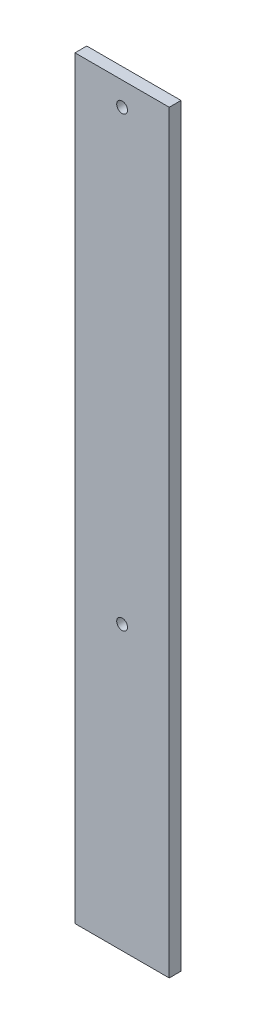
SolidWorks part; units mm, degrees
ref_plane "Front Plane" through (0, 0, 0) normal (0, 0, 1) x (1, 0, 0)
ref_plane "Top Plane" through (0, 0, 0) normal (0, 1, 0) x (1, 0, 0)
ref_plane "Right Plane" through (0, 0, 0) normal (1, 0, 0) x (0, 0, -1)
sketch "Sketch2" plane through (0, 0, 0) normal (0, 0, 1) x (1, 0, 0)
  line L0 (12.7, 203.2) -> (12.7, 0) construction
  line L1 (0, 0) -> (25.4, 0)
  line L2 (0, 0) -> (0, 203.2)
  line L3 (0, 203.2) -> (25.4, 203.2)
  line L4 (25.4, 0) -> (25.4, 203.2)
  circle A0 centre (12.7, 196.85) radius 1.4605
  circle A1 centre (12.7, 76.2) radius 1.4605
  dimension "D3" = 2.921
  dimension "D5" = 2.921
  dimension "D1" = 25.4
  dimension "D2" = 203.2
  dimension "D4" = 6.35
  dimension "D6" = 120.65
extrude "Boss-Extrude1" add sketch "Sketch2" along normal blind 3.175
